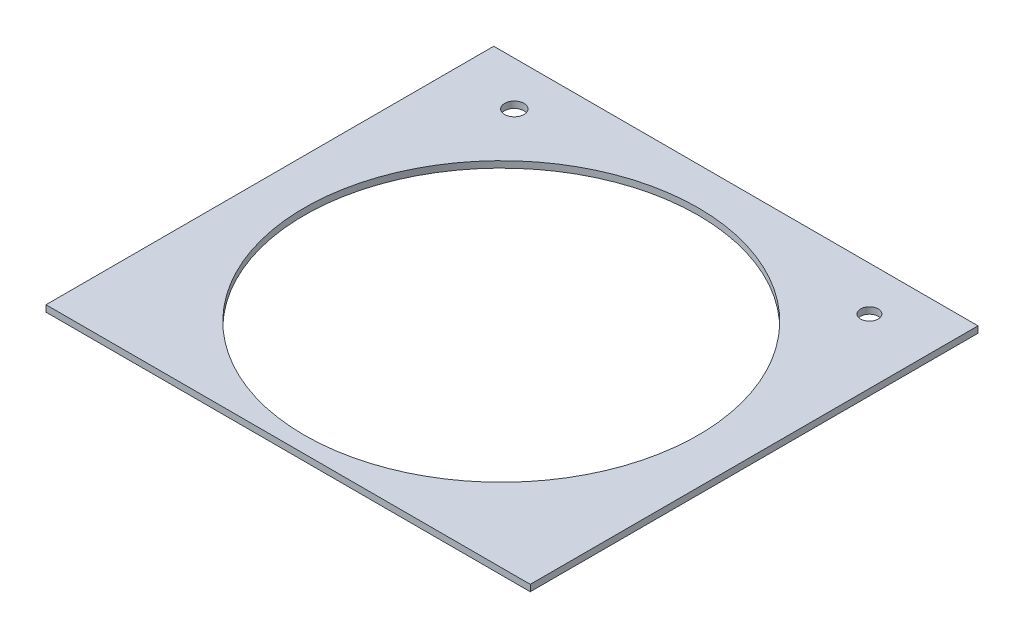
SolidWorks part; units mm, degrees
ref_plane "Front Plane" through (0, 0, 0) normal (0, 0, 1) x (1, 0, 0)
ref_plane "Top Plane" through (0, 0, 0) normal (0, 1, 0) x (1, 0, 0)
ref_plane "Right Plane" through (0, 0, 0) normal (1, 0, 0) x (0, 0, -1)
sketch "Sketch1" plane through (0, 0, 0) normal (0, 1, 0) x (1, 0, 0)
  line L3 (-37.5, 34.8346) -> (37.5, 34.8346)
  line L4 (37.5, -34.51) -> (37.5, 34.8346)
  line L5 (-37.5, -34.51) -> (37.5, -34.51)
  line L11 (-37.5, 34.8346) -> (-37.5, -34.51)
  circle A0 centre (-27.5, 28.0164) radius 1.5
  circle A1 centre (27.5, 28.0164) radius 1.3636
  circle A4 centre (0, -1.5) radius 30.5
  point P0 (0, 0)
  point P5 (0, 0)
  point P16 (0, 29)
  dimension "D1" = 75
  dimension "D2" = 55
extrude "Boss-Extrude1" add sketch "Sketch1" along normal blind 1
